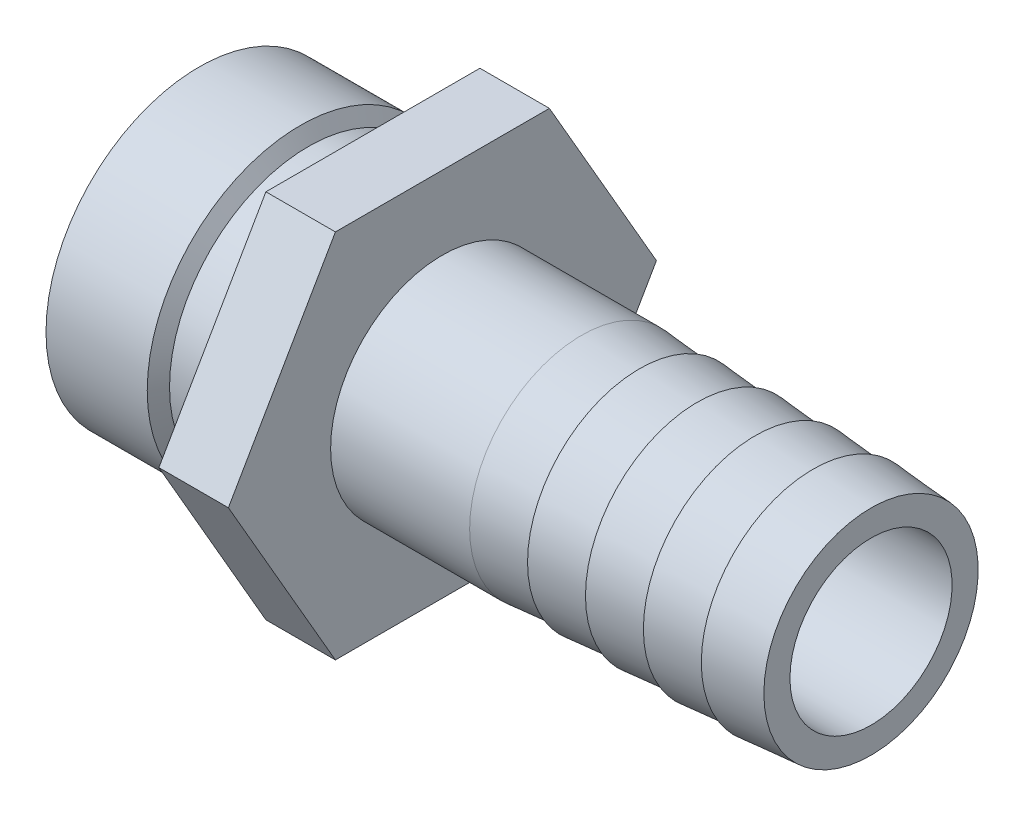
SolidWorks part; units mm, degrees
material "V4a"
ref_plane "Vorne" through (0, 0, 0) normal (0, 0, 1) x (1, 0, 0)
ref_plane "Oben" through (0, 0, 0) normal (0, 1, 0) x (1, 0, 0)
ref_plane "Rechts" through (0, 0, 0) normal (1, 0, 0) x (0, 0, -1)
sketch "Skizze2" plane through (0, 0, 0) normal (0, 0, 1) x (1, 0, 0)
  line L0 (-12.8257, 0) -> (37.1476, 0) construction
  line L1 (5, 13.22) -> (5, 9.65)
  line L2 (5, 9.65) -> (21, 9.65)
  line L6 (38, 9.65) -> (43, 9.25)
  line L7 (48, 9.25) -> (48, 7)
  line L8 (48, 7) -> (-10, 7)
  line L9 (5, 13.22) -> (-10, 13.22)
  line L10 (-10, 13.22) -> (-10, 7)
  line L11 (43, 9.65) -> (48, 9.25)
  line L12 (43, 9.65) -> (43, 9.25)
  line L13 (38, 9.65) -> (38, 9.25)
  line L14 (33, 9.65) -> (38, 9.25)
  line L15 (33, 9.65) -> (33, 9.25)
  line L16 (28, 9.65) -> (33, 9.25)
  line L17 (28, 9.65) -> (28, 9.25)
  line L18 (23, 9.65) -> (28, 9.25)
  line L19 (23, 9.65) -> (21, 9.65)
  line L20 (23, 9.65) -> (23, 9.25) [skipped]
  dimension "D2" = 10
  dimension "D3" = 15
  dimension "D4" = 58
  dimension "D5" = 19.3
  dimension "D6" = 14
  dimension "D8" = 26.44
  dimension "D9" = 18.5
  dimension "D11" = 5
revolve "Rotation1" add sketch "Skizze2" angle 360 about L0
ref_plane "Ebene1" through (5, 0, 0) normal (-1, 0, 0) x (0, 0, 1)
sketch "Skizze4" plane through (5, 0, 0) normal (-1, 0, 0) x (0, 0, 1)
  line L0 (20.3227, 0) -> (-20.3227, 0) construction
  line L1 (9.2376, -16) -> (18.4752, 0)
  line L2 (18.4752, 0) -> (9.2376, 16)
  line L3 (9.2376, 16) -> (-9.2376, 16)
  line L4 (-9.2376, 16) -> (-18.4752, 0)
  line L5 (-18.4752, 0) -> (-9.2376, -16)
  line L6 (-9.2376, -16) -> (9.2376, -16)
  circle A0 centre (0, 0) radius 16 construction
  dimension "D1" = 32
extrude "Linear austragen1" add sketch "Skizze4" against normal blind 6
sketch "Skizze5" plane through (0, 0, 0) normal (0, 0, 1) x (1, 0, 0)
  line L0 (-2, 14.5) -> (-0.5566, 12)
  line L2 (-0.5566, 12) -> (5, 12)
  line L4 (5, 12) -> (5, 14.5)
  line L5 (5, 14.5) -> (-2, 14.5)
  line L6 (-12.8257, 0) -> (37.1476, 0) construction
  line L7 (5, 0) -> (5, 16) construction
  dimension "D1" = 12
  dimension "D2" = 60
  dimension "D3" = 2.5
  dimension "D4" = 7
revolve "Schnitt-Rotation1" cut sketch "Skizze5" angle 360 about axis through (-12.8257, 0, 0) along (1, 0, 0)
other "APunkt3" parameters "Durchmesser"=26.8, "Stumpflänge"=0
ref_axis "Achse3" through (21, 0, 0) along (-1, 0, 0)
